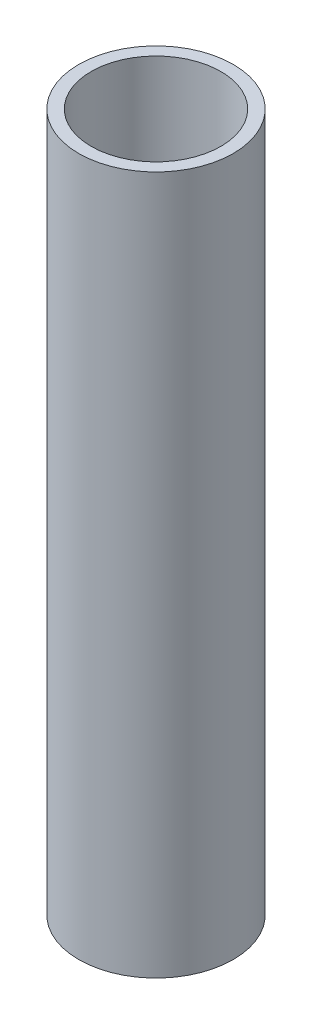
SolidWorks part; units mm, degrees
ref_plane "Front Plane" through (0, 0, 0) normal (0, 0, 1) x (1, 0, 0)
ref_plane "Top Plane" through (0, 0, 0) normal (0, 1, 0) x (1, 0, 0)
ref_plane "Right Plane" through (0, 0, 0) normal (1, 0, 0) x (0, 0, -1)
sketch "Sketch1" plane through (0, 0, 0) normal (0, 1, 0) x (1, 0, 0)
  circle A0 centre (0, 0) radius 12.5
  circle A1 centre (0, 0) radius 10.5
  dimension "D1" = 25
  dimension "D2" = 21
extrude "Boss-Extrude1" add sketch "Sketch1" along normal blind 113
equation "\"cf_tube_outer_diameter\"= 25mm"
equation "\"cf_tube_inner_diameter\" = 21mm"
equation "\"mid_plate_mid_to_top\" = 100mm"
equation "\"mid_plate_mid_to_bottom\" = 30mm"
equation "\"mid_plate_horizontal_spacing\"=250mm"
equation "\"cf_plate_thickness\" =4mm"
equation "\"mid_tube_length\" = 121mm"
equation "\"D1@Sketch1\"=\"cf_tube_outer_diameter\""
equation "\"D2@Sketch1\"=\"cf_tube_inner_diameter\""
